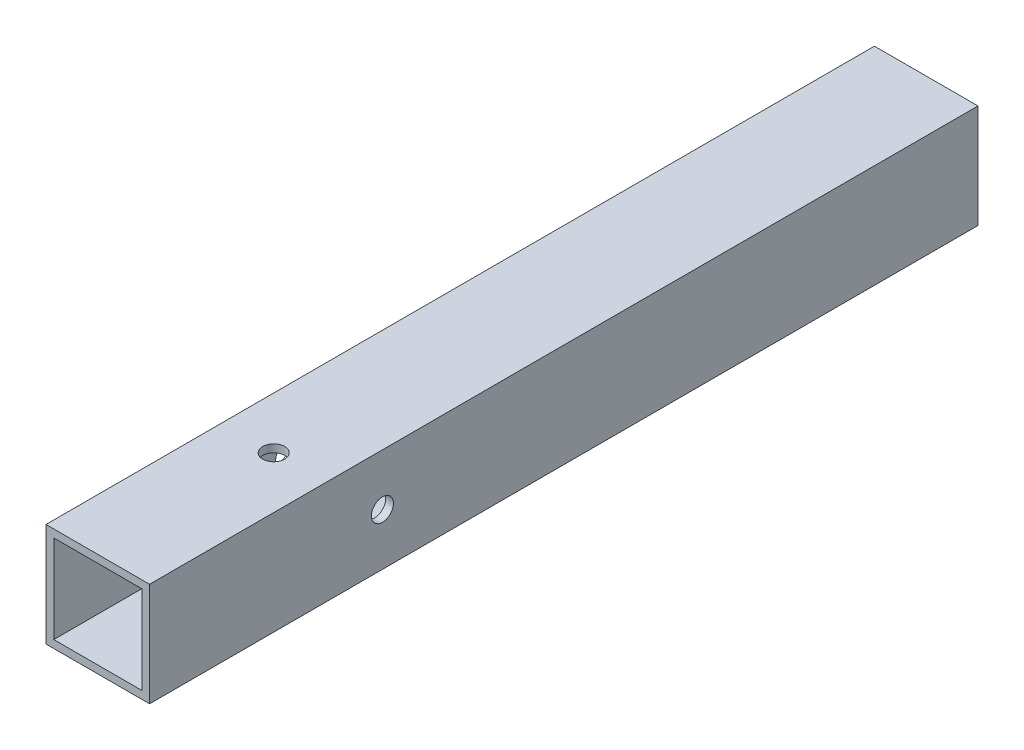
SolidWorks part; units mm, degrees
ref_plane "Front Plane" through (0, 0, 0) normal (0, 0, 1) x (1, 0, 0)
ref_plane "Top Plane" through (0, 0, 0) normal (0, 1, 0) x (1, 0, 0)
ref_plane "Right Plane" through (0, 0, 0) normal (1, 0, 0) x (0, 0, -1)
sketch "Sketch1" plane through (0, 0, 0) normal (0, 0, 1) x (1, 0, 0)
  line L0 (-8.5, -8.5) -> (8.5, -8.5)
  line L1 (-10, -10) -> (10, -10)
  line L2 (-10, -10) -> (-10, 10)
  line L3 (-10, 10) -> (10, 10)
  line L4 (10, -10) -> (10, 10)
  line L5 (-10, -10) -> (10, 10) construction
  line L6 (-10, 10) -> (10, -10) construction
  line L7 (8.5, -8.5) -> (8.5, 8.5)
  line L8 (-8.5, 8.5) -> (8.5, 8.5)
  line L9 (-8.5, -8.5) -> (-8.5, 8.5)
  point P0 (0, 0)
  dimension "D1" = 20
  dimension "D3" = 20
  dimension "D2" = 1.5
extrude "Boss-Extrude1" add sketch "Sketch1" against normal blind 160
sketch "Sketch2" plane through (0, 10, 0) normal (0, 1, 0) x (1, 0, 0)
  line L0 (10, 0) -> (-10, 0) construction
  circle A0 centre (0, 33.975) radius 2.125
  dimension "D1" = 4.25
  dimension "D2" = 33.975
extrude "Cut-Extrude1" cut sketch "Sketch2" against normal through all
sketch "Sketch3" plane through (-10, 0, 0) normal (-1, 0, 0) x (0, 0, 1)
  circle A0 centre (-44.975, 0) radius 2.125
  dimension "D1" = 4.25
  dimension "D2" = 44.975
extrude "Cut-Extrude2" cut sketch "Sketch3" against normal through all
